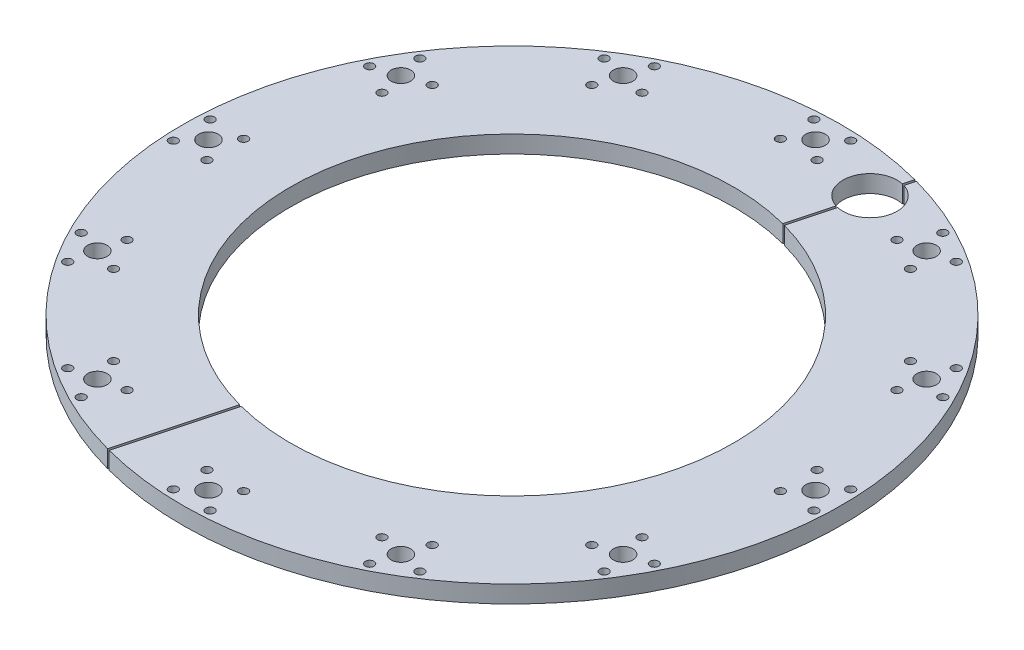
SolidWorks part; units mm, degrees
material "Balsa"
ref_plane "Ebene vorne" through (0, 0, 0) normal (0, 0, 1) x (1, 0, 0)
ref_plane "Ebene oben" through (0, 0, 0) normal (0, 1, 0) x (1, 0, 0)
ref_plane "Ebene rechts" through (0, 0, 0) normal (1, 0, 0) x (0, 0, -1)
sketch "Sketch1" plane through (0, 0, 0) normal (0, 1, 0) x (1, 0, 0)
  circle A0 centre (0, 0) radius 51.2
  circle A1 centre (0, 0) radius 76.1
  dimension "D1" = 152.2
  dimension "D2" = 102.4
extrude "Boss-Extrude1" add sketch "Sketch1" along normal blind 4
sketch "Sketch2" plane through (0, 4, 0) normal (0, 1, 0) x (1, 0, 0)
  line L0 (0, 78.5044) -> (0, 60.1888) construction
  line L1 (7.9546, 70.0914) -> (-11.9341, 70.0914) construction
  circle A0 centre (0, 70.0914) radius 2.25
  circle A1 centre (4.2466, 73.9682) radius 1
  circle A2 centre (4.2466, 66.2147) radius 1
  circle A3 centre (-4.2466, 66.2147) radius 1
  circle A4 centre (-4.2466, 73.9682) radius 1
  point P15 (0, 0)
  point P16 (0, 0)
  point P17 (0, 0)
  point P18 (0, 0)
  point P19 (0, 0)
  point P20 (0, 0)
  point P21 (4.2466, 66.0318)
  dimension "D1" = 4.5
  dimension "D3" = 2
  dimension "D2" = 11.5
extrude "Cut-Extrude1" cut sketch "Sketch2" against normal through all
ref_axis "Axis1" through (0, -0.2, 0) along (0, 1, 0)
pattern_circular "CirPattern1" count 12 over 360 about axis through (0, -0.2, 0) along (0, 1, 0) of "Cut-Extrude1"
sketch "Sketch3" plane through (0, 4, 0) normal (0, 1, 0) x (1, 0, 0)
  line L0 (17.4703, 65.2) -> (0, 0) construction
  line L1 (0, 0) -> (0, 80.521) construction
  circle A0 centre (17.4703, 65.2) radius 6.25
  dimension "D1" = 12.5
  dimension "D3" = 15
  dimension "D2" = 67.5
extrude "Cut-Extrude2" cut sketch "Sketch3" against normal blind 10
sketch "Sketch4" plane through (0, 4, 0) normal (0, 1, 0) x (1, 0, 0)
  line L0 (17.4703, 65.2) -> (0, 0) construction
  line L1 (21.6676, 79.8986) -> (-26.2779, -99.0362)
  line L2 (-26.2779, -99.0362) -> (-26.7608, -98.9068)
  line L3 (-26.7608, -98.9068) -> (21.1846, 80.028)
  line L4 (21.1846, 80.028) -> (21.6676, 79.8986)
  dimension "D1" = 0.5
extrude "Cut-Extrude3" cut sketch "Sketch4" against normal through all
